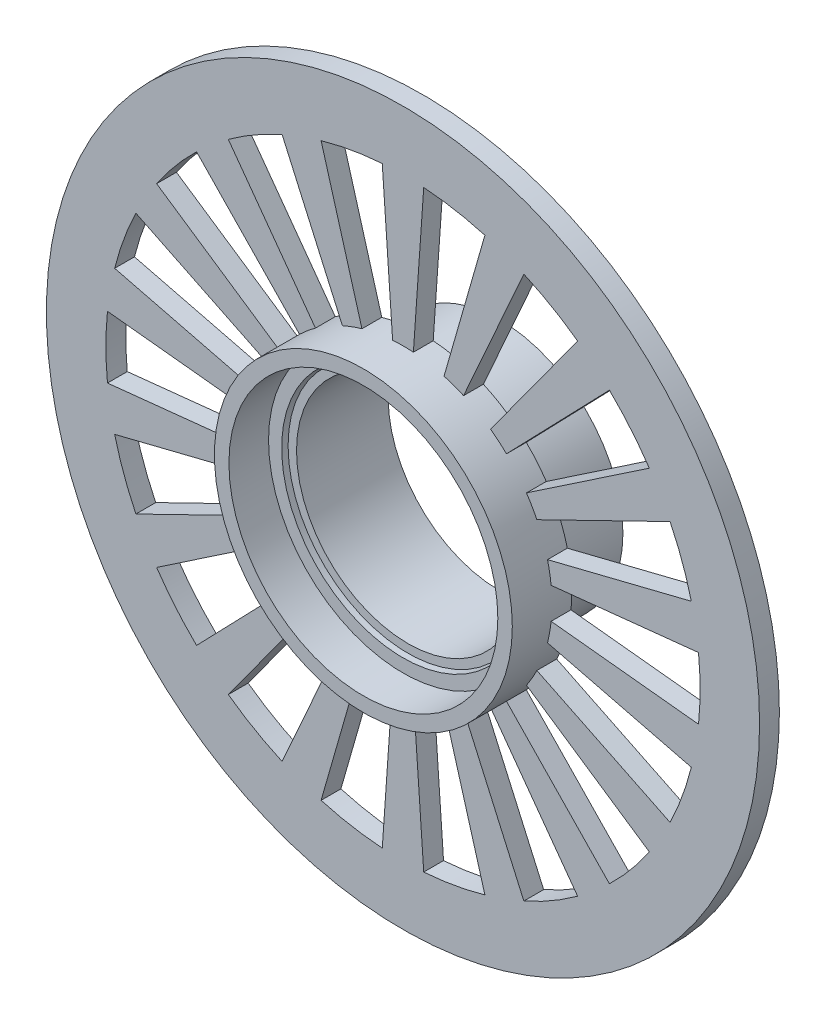
SolidWorks part; units mm, degrees
ref_plane "Front Plane" through (0, 0, 0) normal (0, 0, 1) x (1, 0, 0)
ref_plane "Top Plane" through (0, 0, 0) normal (0, 1, 0) x (1, 0, 0)
ref_plane "Right Plane" through (0, 0, 0) normal (1, 0, 0) x (0, 0, -1)
ref_plane "Plane1" through (0, 0, 19.4878) normal (0, 0, 1) x (1, 0, 0)
sketch "Sketch1" plane through (0, 0, 19.4878) normal (0, 0, 1) x (1, 0, 0)
  circle A0 centre (0, 0) radius 36
  circle A1 centre (0, 0) radius 12.5 construction
  circle A2 centre (0, 0) radius 11.25
  dimension "D1" = 72
  dimension "D2" = 25
  dimension "D3" = 22.5
extrude "Boss-Extrude1" add sketch "Sketch1" along normal blind 2
sketch "Sketch2" plane through (0, 0, 21.4878) normal (0, 0, 1) x (1, 0, 0)
  line L0 (0, 0) -> (0, 36) construction
  line L1 (0, 0) -> (12.3127, 33.8289) construction
  line L2 (0, 0) -> (2.5112, 35.9123) construction
  line L3 (0, 0) -> (9.9229, 34.6054) construction
  line L4 (2.5112, 35.9123) -> (0, 36) construction
  line L5 (9.9229, 34.6054) -> (12.3127, 33.8289) construction
  line L6 (2.0927, 29.9269) -> (1.0489, 15)
  line L7 (8.2691, 28.8379) -> (4.1447, 14.4541)
  line L8 (17.6336, 24.2705) -> (8.8383, 12.1649)
  line L9 (12.2021, 27.4064) -> (6.1159, 13.7366)
  line L10 (24.8711, 16.7758) -> (12.4659, 8.4084)
  line L11 (20.8398, 21.5802) -> (10.4453, 10.8164)
  line L12 (29.1089, 7.2577) -> (14.59, 3.6377)
  line L13 (26.9638, 13.1511) -> (13.5148, 6.5916)
  line L14 (29.8357, -3.1359) -> (14.9543, -1.5718)
  line L15 (29.8357, 3.1359) -> (14.9543, 1.5718)
  line L16 (26.9638, -13.1511) -> (13.5148, -6.5916)
  line L17 (29.1089, -7.2577) -> (14.59, -3.6377)
  line L18 (20.8398, -21.5802) -> (10.4453, -10.8164)
  line L19 (24.8711, -16.7758) -> (12.4659, -8.4084)
  line L20 (12.2021, -27.4064) -> (6.1159, -13.7366)
  line L21 (17.6336, -24.2705) -> (8.8383, -12.1649)
  line L22 (2.0927, -29.9269) -> (1.0489, -15)
  line L23 (8.2691, -28.8379) -> (4.1447, -14.4541)
  line L24 (-8.2691, -28.8379) -> (-4.1447, -14.4541)
  line L25 (-2.0927, -29.9269) -> (-1.0489, -15)
  line L26 (-17.6336, -24.2705) -> (-8.8383, -12.1649)
  line L27 (-12.2021, -27.4064) -> (-6.1159, -13.7366)
  line L28 (-24.8711, -16.7758) -> (-12.4659, -8.4084)
  line L29 (-20.8398, -21.5802) -> (-10.4453, -10.8164)
  line L30 (-29.1089, -7.2577) -> (-14.59, -3.6377)
  line L31 (-26.9638, -13.1511) -> (-13.5148, -6.5916)
  line L32 (-29.8357, 3.1359) -> (-14.9543, 1.5718)
  line L33 (-29.8357, -3.1359) -> (-14.9543, -1.5718)
  line L34 (-26.9638, 13.1511) -> (-13.5148, 6.5916)
  line L35 (-29.1089, 7.2577) -> (-14.59, 3.6377)
  line L36 (-20.8398, 21.5802) -> (-10.4453, 10.8164)
  line L37 (-24.8711, 16.7758) -> (-12.4659, 8.4084)
  line L38 (-12.2021, 27.4064) -> (-6.1159, 13.7366)
  line L39 (-17.6336, 24.2705) -> (-8.8383, 12.1649)
  line L40 (-2.0927, 29.9269) -> (-1.0489, 15)
  line L41 (-8.2691, 28.8379) -> (-4.1447, 14.4541)
  circle A0 centre (0, 0) radius 36 construction
  arc A1 (2.0927, 29.9269) -> (8.2691, 28.8379) centre (0, 0) cw
  arc A2 (1.0489, 15) -> (4.1447, 14.4541) centre (0, 0) cw
  circle A3 centre (0, 0) radius 11.25 construction
  arc A4 (6.1159, 13.7366) -> (8.8383, 12.1649) centre (0, 0) cw
  arc A5 (12.2021, 27.4064) -> (17.6336, 24.2705) centre (0, 0) cw
  arc A6 (10.4453, 10.8164) -> (12.4659, 8.4084) centre (0, 0) cw
  arc A7 (20.8398, 21.5802) -> (24.8711, 16.7758) centre (0, 0) cw
  arc A8 (13.5148, 6.5916) -> (14.59, 3.6377) centre (0, 0) cw
  arc A9 (26.9638, 13.1511) -> (29.1089, 7.2577) centre (0, 0) cw
  arc A10 (14.9543, 1.5718) -> (14.9543, -1.5718) centre (0, 0) cw
  arc A11 (29.8357, 3.1359) -> (29.8357, -3.1359) centre (0, 0) cw
  arc A12 (14.59, -3.6377) -> (13.5148, -6.5916) centre (0, 0) cw
  arc A13 (29.1089, -7.2577) -> (26.9638, -13.1511) centre (0, 0) cw
  arc A14 (12.4659, -8.4084) -> (10.4453, -10.8164) centre (0, 0) cw
  arc A15 (24.8711, -16.7758) -> (20.8398, -21.5802) centre (0, 0) cw
  arc A16 (8.8383, -12.1649) -> (6.1159, -13.7366) centre (0, 0) cw
  arc A17 (17.6336, -24.2705) -> (12.2021, -27.4064) centre (0, 0) cw
  arc A18 (4.1447, -14.4541) -> (1.0489, -15) centre (0, 0) cw
  arc A19 (8.2691, -28.8379) -> (2.0927, -29.9269) centre (0, 0) cw
  arc A20 (-1.0489, -15) -> (-4.1447, -14.4541) centre (0, 0) cw
  arc A21 (-2.0927, -29.9269) -> (-8.2691, -28.8379) centre (0, 0) cw
  arc A22 (-6.1159, -13.7366) -> (-8.8383, -12.1649) centre (0, 0) cw
  arc A23 (-12.2021, -27.4064) -> (-17.6336, -24.2705) centre (0, 0) cw
  arc A24 (-10.4453, -10.8164) -> (-12.4659, -8.4084) centre (0, 0) cw
  arc A25 (-20.8398, -21.5802) -> (-24.8711, -16.7758) centre (0, 0) cw
  arc A26 (-13.5148, -6.5916) -> (-14.59, -3.6377) centre (0, 0) cw
  arc A27 (-26.9638, -13.1511) -> (-29.1089, -7.2577) centre (0, 0) cw
  arc A28 (-14.9543, -1.5718) -> (-14.9543, 1.5718) centre (0, 0) cw
  arc A29 (-29.8357, -3.1359) -> (-29.8357, 3.1359) centre (0, 0) cw
  arc A30 (-14.59, 3.6377) -> (-13.5148, 6.5916) centre (0, 0) cw
  arc A31 (-29.1089, 7.2577) -> (-26.9638, 13.1511) centre (0, 0) cw
  arc A32 (-12.4659, 8.4084) -> (-10.4453, 10.8164) centre (0, 0) cw
  arc A33 (-24.8711, 16.7758) -> (-20.8398, 21.5802) centre (0, 0) cw
  arc A34 (-8.8383, 12.1649) -> (-6.1159, 13.7366) centre (0, 0) cw
  arc A35 (-17.6336, 24.2705) -> (-12.2021, 27.4064) centre (0, 0) cw
  arc A36 (-4.1447, 14.4541) -> (-1.0489, 15) centre (0, 0) cw
  arc A37 (-8.2691, 28.8379) -> (-2.0927, 29.9269) centre (0, 0) cw
  point P85 (0, 0)
  dimension "D1" = 20
  dimension "D2" = 4
  dimension "D3" = 6
  dimension "D4" = 15
  dimension "D5" = 18
extrude "Cut-Extrude1" cut sketch "Sketch2" against normal through all
sketch "Sketch3" plane through (0, 0, 19.4878) normal (0, 0, -1) x (-1, 0, 0)
  circle A0 centre (0, 0) radius 12.45
  circle A1 centre (0, 0) radius 11.25 construction
  circle A2 centre (0, 0) radius 11.25
  dimension "D1" = 24.9
extrude "Boss-Extrude2" add sketch "Sketch3" along normal offset from surface (7.754 mm away) 2 offset beyond the face yes
split "Split1" bodies to split 103 resulting bodies 104 105 split by face at (36, 0, 19.4878)
sketch "Sketch4" plane through (0, 0, 21.4878) normal (0, 0, 1) x (1, 0, 0)
  circle A0 centre (0, 0) radius 12.25
  circle A1 centre (0, 0) radius 11.25 construction
  circle A2 centre (0, 0) radius 11.25
  dimension "D1" = 1
extrude "Cut-Extrude2" cut sketch "Sketch4" against normal up to surface (2 mm away) up to face at (-11.25, 0, 19.4878)
sketch "Sketch5" plane through (0, 0, 19.4878) normal (0, 0, 1) x (1, 0, 0)
  circle A0 centre (0, 0) radius 11.25 construction
  circle A1 centre (0, 0) radius 11.25
  circle A2 centre (0, 0) radius 12.25 construction
  circle A3 centre (0, 0) radius 12.25 construction
  circle A4 centre (0, 0) radius 12.1
  dimension "D1" = 0.15
extrude "Boss-Extrude3" add sketch "Sketch5" along normal offset from surface (1.5 mm away) 0.5 separate body up to face at (12.25, 0, 21.4878)
sketch "Sketch6" plane through (0, 0, 21.4878) normal (0, 0, 1) x (1, 0, 0)
  circle A0 centre (0, 0) radius 13.575
  circle A1 centre (0, 0) radius 15.0366
  dimension "D1" = 27.15
extrude "Boss-Extrude4" add sketch "Sketch6" along normal blind 4
ref_axis "Axis1" through (0, 0, 19.4878) along (0, 0, -1)
combine bodies "Combine1" operation type add bodies to combine 106 108
combine bodies "Combine2" operation type add bodies to combine 107 104
